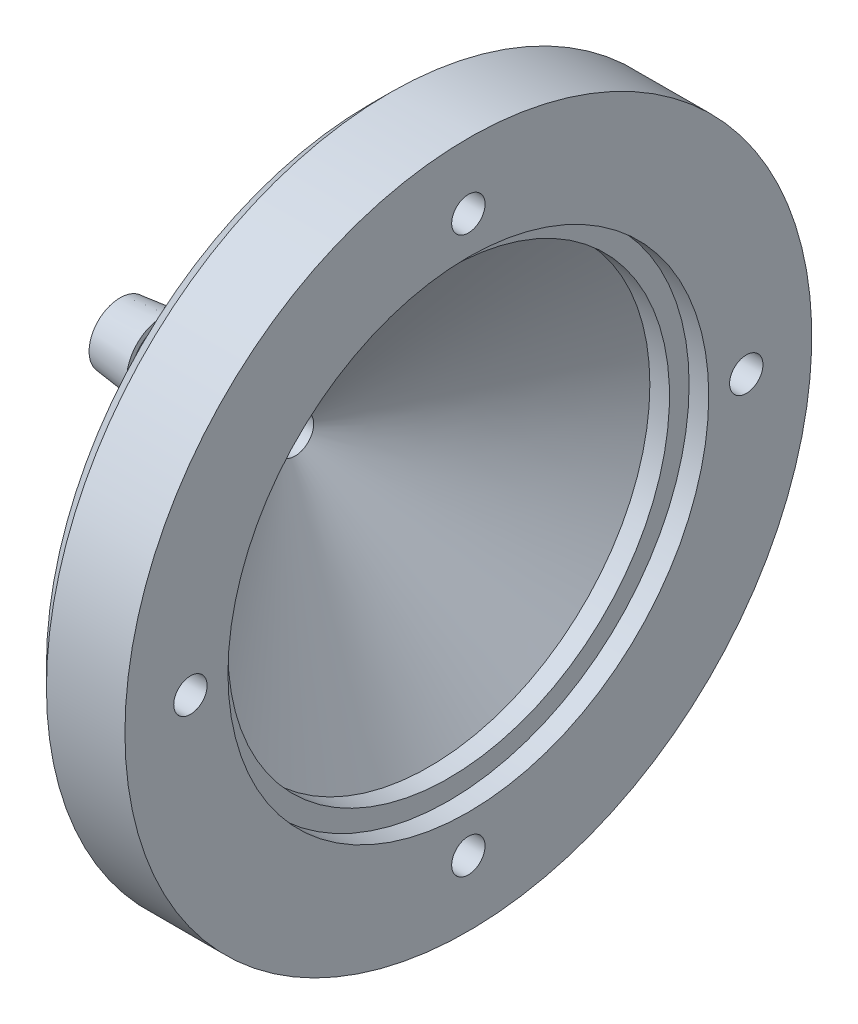
SolidWorks part; units mm, degrees
ref_plane "Front Plane" through (0, 0, 0) normal (0, 0, 1) x (1, 0, 0)
ref_plane "Top Plane" through (0, 0, 0) normal (0, 1, 0) x (1, 0, 0)
ref_plane "Right Plane" through (0, 0, 0) normal (1, 0, 0) x (0, 0, -1)
sketch "Sketch1" plane through (0, 0, 0) normal (0, 0, 1) x (1, 0, 0)
  line L0 (-801.9206, 0) -> (36107.5283, 0) construction
  line L3 (-13.5058, 3.65) -> (-13.5058, 3.15)
  line L8 (-17.8392, 1.9) -> (0, 1.9)
  line L9 (-17.8392, 1.9) -> (-17.8392, 3.15)
  line L10 (17.6645, 24.5) -> (17.6645, 35)
  line L12 (17.6645, 35) -> (7.6645, 35)
  line L16 (17.6645, 24.5) -> (15.6645, 24.5)
  line L17 (15.6645, 24.5) -> (15.6645, 22.5)
  line L18 (7.6645, 35) -> (7.6645, 22.5)
  line L20 (0, 1.9) -> (13.6645, 22.5)
  line L21 (-17.8392, 3.15) -> (-13.5058, 3.65)
  line L22 (13.6645, 22.5) -> (15.6645, 22.5)
  line L23 (-13.5058, 3.15) -> (-9.1725, 3.65)
  line L25 (-9.1725, 3.15) -> (-4.8392, 3.65)
  line L26 (-9.1725, 3.65) -> (-9.1725, 3.15)
  line L27 (-4.8392, 3.65) -> (7.6645, 22.5)
  dimension "D3" = 2
  dimension "D2" = 7.3
  dimension "D6" = 3.8
  dimension "D7" = 6.3
  dimension "D1" = 10
  dimension "D5" = 35
  dimension "D8" = 24.5
  dimension "D10" = 2
  dimension "D9" = 2
  dimension "D11" = 13
  dimension "D4" = 5
revolve "Revolve17" add sketch "Sketch1" angle 360 about L0
sketch "Sketch4" plane through (7.6645, 0, 0) normal (-1, 0, 0) x (0, 0, 1)
  circle A0 centre (0, 0) radius 28.325 construction
  point P3 (0, 28.325)
  point P7 (28.325, 0)
  point P12 (-28.325, 0)
  point P13 (0, -28.325)
  point P19 (0, 0)
  dimension "D1" = 56.65
hole_wizard "CBORE for M3 Hex Socket Head Cap Screw2" positions "Sketch4" profile "Sketch5" counterbore size "M3" standard "ISO"
sketch "Sketch5" plane through (7.6645, -28.325, 0) normal (0, 1, 0) x (0, 0, 1)
  line L0 (0, 0) -> (0, 11.0215)
  line L1 (0, 11.0215) -> (1.7, 10)
  line L2 (1.7, 10) -> (1.7, 3.4)
  line L3 (1.7, 3.4) -> (3.25, 3.4)
  line L4 (3.25, 3.4) -> (3.25, 0)
  line L5 (3.25, 0) -> (0, 0)
  line L10 (0, 11.0215) -> (-1.7, 10) construction
  line L11 (0, -6.35) -> (0, 107.95) construction
  dimension "Hole Dia." = 3.4
  dimension "Hole Depth" = 10
  dimension "C'Bore Dia." = 6.5
  dimension "C'Bore Depth" = 3.4
  dimension "Drill Angle" = 118
chamfer "Chamfer1" distance 2 angle 45 1 edges at (7.6645, 0, 35)
equation "\"D10@Sketch1\"=\"D3@Sketch1\""
equation "\"D9@Sketch1\"=\"D3@Sketch1\""
